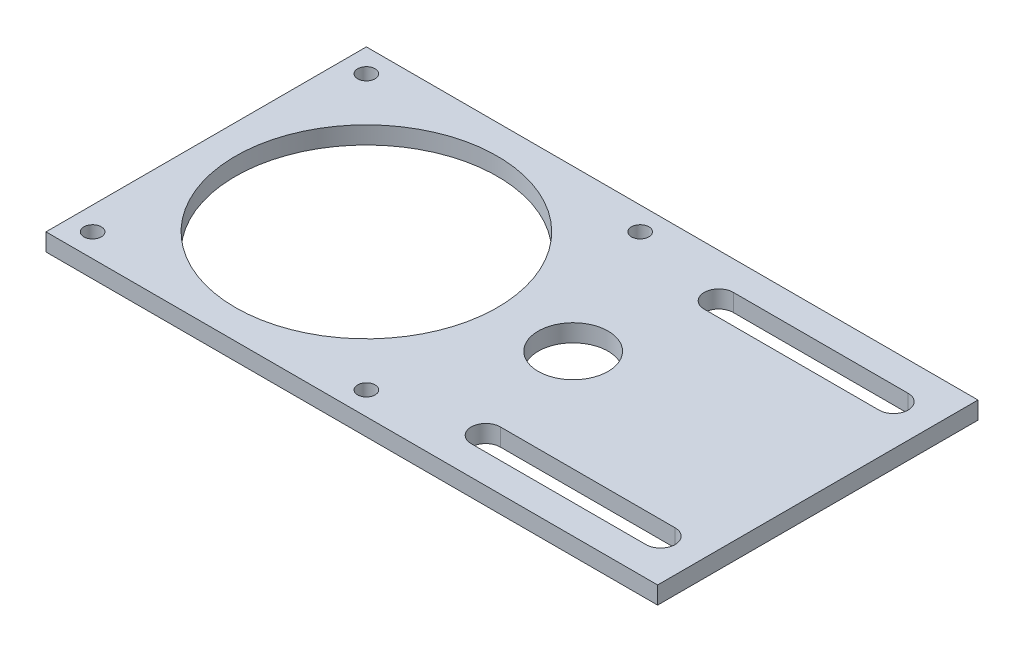
SolidWorks part; units mm, degrees
ref_plane "Front Plane" through (0, 0, 0) normal (0, 0, 1) x (1, 0, 0)
ref_plane "Top Plane" through (0, 0, 0) normal (0, 1, 0) x (1, 0, 0)
ref_plane "Right Plane" through (0, 0, 0) normal (1, 0, 0) x (0, 0, -1)
sketch "Sketch1" plane through (0, 0, 0) normal (0, 1, 0) x (1, 0, 0)
  line L0 (98, 47.5) -> (68, 47.5) construction
  line L1 (0, 0) -> (105, 0)
  line L2 (0, 0) -> (0, 55)
  line L3 (0, 55) -> (105, 55)
  line L4 (105, 0) -> (105, 55)
  line L5 (98, 45) -> (68, 45)
  line L6 (98, 50) -> (68, 50)
  line L7 (98, 7.5) -> (68, 7.5) construction
  line L8 (98, 5) -> (68, 5)
  line L9 (98, 10) -> (68, 10)
  circle A0 centre (27.5, 27.5) radius 22.5
  arc A1 (98, 45) -> (98, 50) centre (98, 47.5) ccw
  arc A2 (68, 50) -> (68, 45) centre (68, 47.5) ccw
  arc A3 (98, 5) -> (98, 10) centre (98, 7.5) ccw
  arc A4 (68, 10) -> (68, 5) centre (68, 7.5) ccw
  circle A5 centre (63, 27.5) radius 6
  circle A6 centre (4, 4) radius 1.5
  circle A7 centre (51, 4) radius 1.5
  circle A8 centre (51, 51) radius 1.5
  circle A9 centre (4, 51) radius 1.5
  point P9 (83, 47.5)
  point P17 (83, 7.5)
  point P26 (0, 0)
  point P27 (0, 0)
  dimension "D3" = 2
  dimension "D4" = 2
  dimension "D6" = 35.5
  dimension "D1" = 55
  dimension "D2" = 105
  dimension "D5" = 2
extrude "Boss-Extrude1" add sketch "Sketch1" along normal blind 3
ref_axis "Axis1" through (0, 3, -27.5) along (0.9996, -0.0286, 0)
